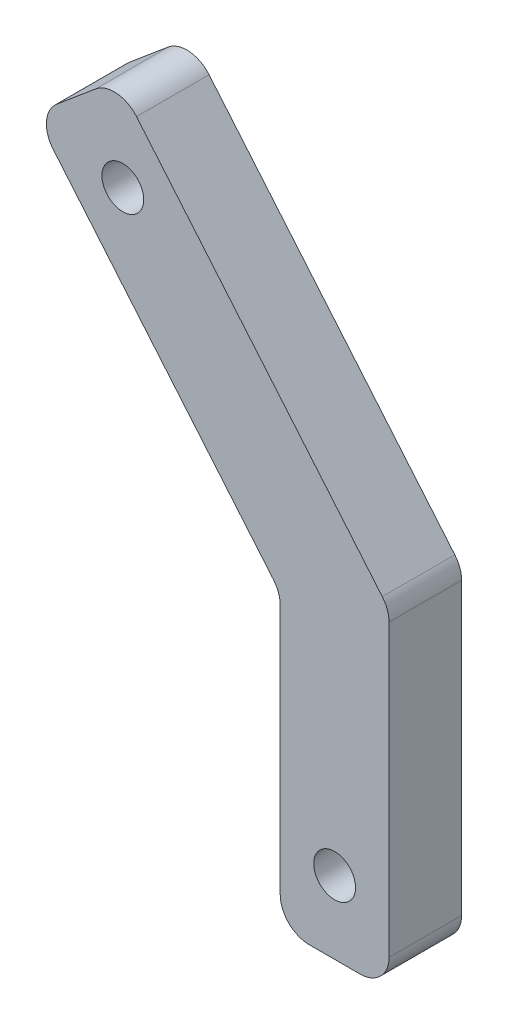
SolidWorks part; units mm, degrees
material "Acrylic (Medium-high impact)"
ref_plane "Front Plane" through (0, 0, 0) normal (0, 0, 1) x (1, 0, 0)
ref_plane "Top Plane" through (0, 0, 0) normal (0, 1, 0) x (1, 0, 0)
ref_plane "Right Plane" through (0, 0, 0) normal (1, 0, 0) x (0, 0, -1)
sketch "Sketch1" plane through (0, 0, 0) normal (0, 0, 1) x (1, 0, 0)
  line L0 (0, 0) -> (7.2966, 6.1226)
  line L1 (7.2966, 6.1226) -> (31.029, -22.1606)
  line L2 (31.029, -22.1606) -> (31.029, -51.0274)
  line L3 (0, 0) -> (21.504, -25.6274)
  line L4 (21.504, -25.6274) -> (21.504, -51.0274)
  line L5 (21.504, -51.0274) -> (31.029, -51.0274)
  dimension "D1" = 9.525
  dimension "D2" = 140
  dimension "D3" = 25.4
  dimension "D4" = 57.15
extrude "Boss-Extrude1" add sketch "Sketch1" along normal blind 6.35
fillet "Fillet1" radius 2.54 6 edges at (7.2966, 6.1226, 3.175) (0, 0, 3.175) (31.029, -51.0274, 3.175) (21.504, -51.0274, 3.175) (31.029, -22.1606, 3.175) (21.504, -25.6274, 3.175)
hole_wizard "#6 Clearance Hole1" positions "Sketch2" profile "Sketch3" hole size "#6" standard "ANSI Inch"
sketch "Sketch2" plane through (0, 0, 6.35) normal (0, 0, 1) x (1, 0, 0)
  line L0 (5.3508, 4.4899) -> (1.9458, 1.6327) construction
  line L1 (24.044, -51.0274) -> (28.489, -51.0274) construction
  line L2 (3.6483, 3.0613) -> (11.8117, -6.6675) construction
  line L4 (26.2665, -51.0274) -> (26.2665, -44.6774) construction
  line L6 (30.4347, -21.4524) -> (8.9293, 4.1768) construction
  point P0 (7.73, -1.8031)
  point P2 (26.2665, -44.6774)
  dimension "D1" = 6.35
  dimension "D2" = 6.35
sketch "Sketch3" plane through (7.73, -1.8031, 6.35) normal (1, 0, 0) x (0, -1, 0)
  line L0 (0, 0) -> (0, 11.2589)
  line L1 (0, 11.2589) -> (1.8288, 10.16)
  line L2 (1.8288, 10.16) -> (1.8288, 0)
  line L5 (1.8288, 0) -> (0, 0)
  line L10 (0, 11.2589) -> (-1.8288, 10.16) construction
  line L11 (0, -6.35) -> (0, 107.95) construction
  dimension "Hole Dia." = 3.6576
  dimension "Hole Depth" = 10.16
  dimension "Drill Angle" = 118
